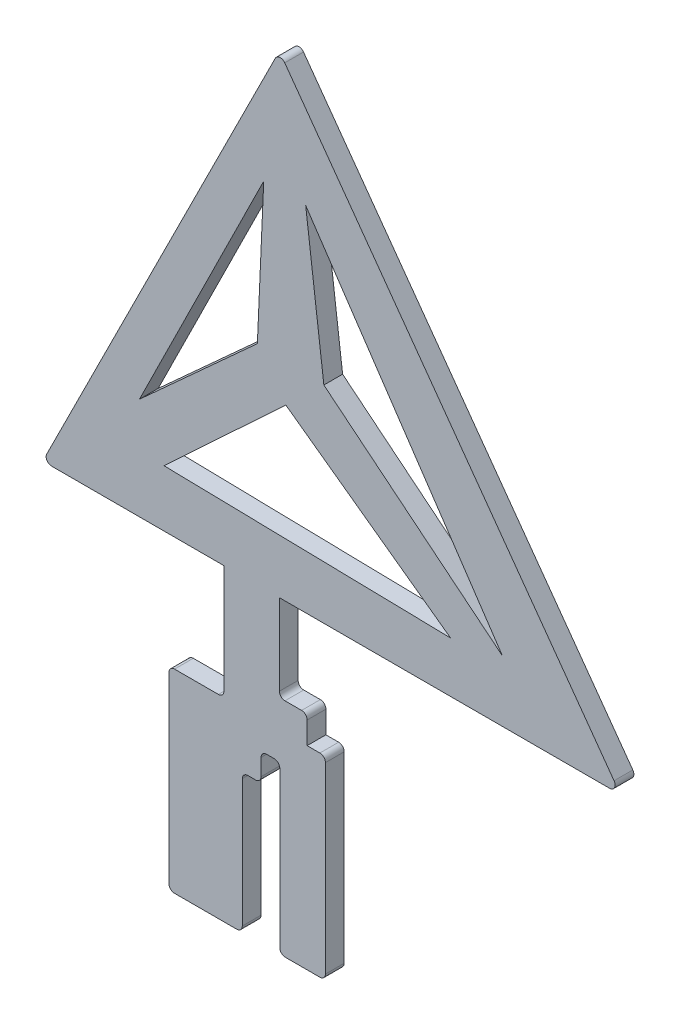
SolidWorks part; units mm, degrees
ref_plane "Front Plane" through (0, 0, 0) normal (0, 0, 1) x (1, 0, 0)
ref_plane "Top Plane" through (0, 0, 0) normal (0, 1, 0) x (1, 0, 0)
ref_plane "Right Plane" through (0, 0, 0) normal (1, 0, 0) x (0, 0, -1)
sketch "Sketch2" plane through (0, 0, 0) normal (0, 0, 1) x (1, 0, 0)
  line L0 (6.35, 101.6) -> (6.35, 156.7234)
  line L1 (-10.541, -22.225) -> (10.541, -22.225)
  line L2 (-10.541, -22.225) -> (-10.541, 22.225)
  line L3 (-10.541, 22.225) -> (10.541, 22.225)
  line L4 (10.541, -22.225) -> (10.541, 22.225)
  line L5 (-10.541, -22.225) -> (10.541, 22.225) construction
  line L6 (-10.541, 22.225) -> (10.541, -22.225) construction
  line L7 (-6.35, 0) -> (6.35, 0)
  line L8 (-6.35, 0) -> (-6.35, 101.6)
  line L9 (-6.35, 101.6) -> (6.35, 101.6)
  line L10 (6.35, 0) -> (6.35, 101.6)
  line L11 (6.35, 156.7234) -> (-47.8282, 48.3844)
  line L12 (-47.8282, 48.3844) -> (-6.35, 48.3844)
  line L13 (6.35, 156.7234) -> (84.4033, 48.3844)
  line L14 (84.4033, 48.3844) -> (6.35, 48.3844)
  point P0 (0, 0)
  point P10 (83.1076, 50.4992)
  point P15 (-46.3098, 51.9546)
  point P17 (6.35, 156.7234)
  dimension "D1" = 21.082
  dimension "D2" = 44.45
  dimension "D3" = 12.7
  dimension "D4" = 101.6
extrude "Boss-Extrude2" add sketch "Sketch2" along normal blind 4.2926 contours L3 L10 L9 L8 | L7 L10 L3 L8 | L10 L7 L8 L3 L2 L1 L4 | L14 L13 L0 L10 | L11 L12 L8 L9 L0 | L8 L7 L10 L9 region at (-15.2126, 87.3411, 0) region at (0, 61.9125, 0) region at (32.3678, 84.4974, 0) region at (0, 11.1125, 0) region at (0, -4.7899, 0)
extrude "Boss-Extrude3" add sketch "Sketch2<3>" along normal blind 4.2926 contours L11 L12 L8 L9 L0 region at (-15.2126, 87.3411, 0)
sketch "Sketch2<3>" plane through (0, 0, 0) normal (0, 0, 1) x (1, 0, 0) same geometry as "Sketch2"
sketch "Sketch5" plane through (0, 0, 0) normal (0, 0, -1) x (-1, 0, 0)
  line L5 (10.541, -22.225) -> (-10.541, -22.225) construction
  line L6 (-2.1463, -22.225) -> (2.1463, -22.225)
  line L7 (-2.1463, -22.225) -> (-2.1463, 9.525)
  line L8 (-2.1463, 9.525) -> (2.1463, 9.525)
  line L9 (2.1463, -22.225) -> (2.1463, 9.525)
  line L10 (-2.1463, -22.225) -> (2.1463, 9.525) construction
  line L11 (-2.1463, 9.525) -> (2.1463, -22.225) construction
  point P0 (0, -6.35)
  dimension "D1" = 31.75
  dimension "D2" = 4.2926
extrude "Cut-Extrude2" cut sketch "Sketch5" against normal blind 4.2926
sketch "Sketch6" plane through (0, 0, 0) normal (0, 0, -1) x (-1, 0, 0)
  line L0 (-6.35, 22.225) -> (-10.541, 22.225) construction
  line L1 (-2.1463, -22.225) -> (-6.4389, -22.225)
  line L2 (-2.1463, -22.225) -> (-2.1463, 15.875)
  line L3 (-2.1463, 15.875) -> (-6.4389, 15.875)
  line L4 (-6.4389, -22.225) -> (-6.4389, 15.875)
  line L5 (-2.1463, -22.225) -> (-6.4389, 15.875) construction
  line L6 (-2.1463, 15.875) -> (-6.4389, -22.225) construction
  line L7 (-2.1463, -22.225) -> (-10.541, -22.225) construction
  line L8 (-2.1463, 9.525) -> (-2.1463, -22.225) construction
  point P0 (-4.2926, -3.175)
  dimension "D1" = 4.2926
  dimension "D2" = 6.35
extrude "Cut-Extrude3" cut sketch "Sketch6" against normal blind 4.2926
sketch "Sketch9" plane through (10.541, 0, 0) normal (1, 0, 0) x (0, 0, -1)
  line L1 (-4.2926, -22.225) -> (0, -22.225)
  line L2 (-4.2926, -22.225) -> (-4.2926, 22.225)
  line L3 (-4.2926, 22.225) -> (0, 22.225)
  line L4 (0, -22.225) -> (0, 22.225)
extrude "Boss-Extrude4" add sketch "Sketch9" along normal blind 6.35
sketch "Sketch10" plane through (6.35, 0, 0) normal (1, 0, 0) x (0, 0, -1)
  line L0 (0, 22.225) -> (0, 48.3844) construction
  line L1 (-4.2926, 22.225) -> (0, 22.225)
  line L2 (-4.2926, 22.225) -> (-4.2926, 28.575)
  line L3 (-4.2926, 28.575) -> (0, 28.575)
  line L4 (0, 22.225) -> (0, 28.575)
  dimension "D1" = 6.35
extrude "Boss-Extrude5" add sketch "Sketch10" along normal blind 6.35
sketch "Sketch12" plane through (-10.541, 0, 0) normal (-1, 0, 0) x (0, 0, 1)
  line L1 (0, -22.225) -> (4.2926, -22.225)
  line L2 (0, -22.225) -> (0, 22.225)
  line L3 (0, 22.225) -> (4.2926, 22.225)
  line L4 (4.2926, -22.225) -> (4.2926, 22.225)
extrude "Boss-Extrude6" add sketch "Sketch12" along normal blind 8.382
fillet "Fillet4" radius 1.27 16 edges at (6.4389, 15.875, 2.1463) (2.1463, 15.875, 2.1463) (-2.1463, 9.525, 2.1463) (2.1463, 9.525, 2.1463) (-6.35, 22.225, 2.1463) (-2.1463, -22.225, 2.1463) (6.4389, -22.225, 2.1463) (16.891, -22.225, 2.1463) (16.891, 22.225, 2.1463) (6.35, 28.575, 2.1463) (12.7, 28.575, 2.1463) (-18.923, -22.225, 2.1463) (-18.923, 22.225, 2.1463) (6.35, 156.7234, 2.1463) (-47.8282, 48.3844, 2.1463) (84.4033, 48.3844, 2.1463)
sketch "Sketch4" plane through (0, 0, 0) normal (0, 0, -1) x (-1, 0, 0)
  line L6 (-2.7612, 129.1446) -> (-1.3085, 96.2201)
  line L7 (-1.3085, 96.2201) -> (25.6894, 71.6984)
  line L8 (25.6894, 71.6984) -> (-2.7612, 129.1446)
  line L9 (-12.3681, 129.1446) -> (-16.5257, 95.6237)
  line L10 (-16.5257, 95.6237) -> (-57.4201, 62.3527)
  line L11 (-57.4201, 62.3527) -> (-12.3681, 129.1446)
  line L15 (-7.8198, 87.3082) -> (-45.5312, 59.9837)
  line L16 (-45.5312, 59.9837) -> (20.0458, 61.3394)
  line L17 (20.0458, 61.3394) -> (-7.8198, 87.3082)
  point P0 (-45.5312, 59.9837)
  point P3 (-8.3458, 86.0298)
extrude "Cut-Extrude1" cut sketch "Sketch4" against normal blind 4.2926
